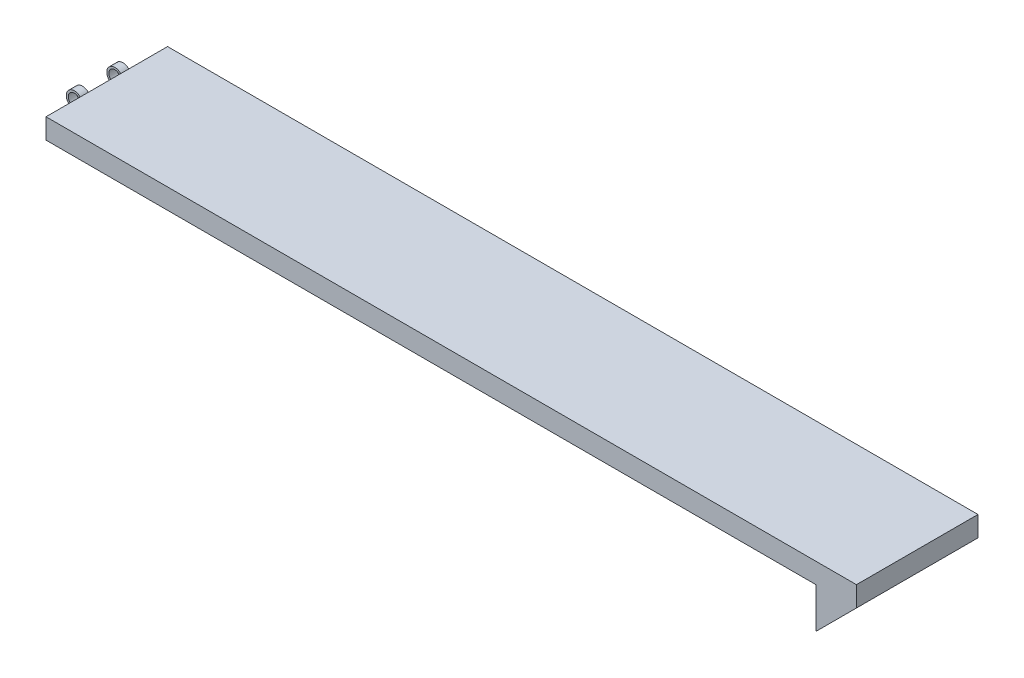
SolidWorks part; units mm, degrees
ref_plane "Front Plane" through (0, 0, 0) normal (0, 0, 1) x (1, 0, 0)
ref_plane "Top Plane" through (0, 0, 0) normal (0, 1, 0) x (1, 0, 0)
ref_plane "Right Plane" through (0, 0, 0) normal (1, 0, 0) x (0, 0, -1)
sketch "Sketch1" plane through (0, 0, 0) normal (0, 1, 0) x (1, 0, 0)
  line L1 (0, 0) -> (254, 0)
  line L2 (0, 0) -> (0, 38.1)
  line L3 (0, 38.1) -> (254, 38.1)
  line L4 (254, 0) -> (254, 38.1)
  dimension "D1" = 254
  dimension "D2" = 38.1
extrude "Boss-Extrude1" add sketch "Sketch1" along normal blind 6.35
ref_plane "Plane1" through (0, 0, -12.7) normal (0, 0, 1) x (1, 0, 0)
sketch "Sketch2" plane through (0, 0, -12.7) normal (0, 0, 1) x (1, 0, 0)
  line L0 (0, 6.35) -> (0, 0) construction
  circle A0 centre (-2.54, 3.8728) radius 2.54
  circle A1 centre (-2.54, 3.8728) radius 1.905
  dimension "D1" = 5.08
  dimension "D3" = 3.81
  dimension "D2" = 3.8728
extrude "Boss-Extrude2" add sketch "Sketch2" along normal blind 1.27 and the other way blind 1.27 separate body
ref_plane "Plane2" through (0, 0, -19.05) normal (0, 0, 1) x (1, 0, 0)
pattern_linear "LPattern1" count 2 spacing 12.7 along (0, 0, -1) of "Boss-Extrude2"
sketch "Sketch4" plane through (0, 0, -19.05) normal (0, 0, 1) x (1, 0, 0)
  circle A5 centre (256.54, 3.8728) radius 1.905
  circle A6 centre (256.54, 3.8728) radius 2.54
  dimension "D3" = 3.81
  dimension "D4" = 5.08
  dimension "D1" = 3.8728
  dimension "D2" = 256.54
sketch "Sketch5" plane through (0, 0, 0) normal (0, -1, 0) x (1, 0, 0)
  line L0 (254, -38.1) -> (0, -38.1) construction
  line L1 (254, 0) -> (241.3, 0)
  line L2 (254, 0) -> (254, -38.1)
  line L3 (254, -38.1) -> (241.3, -38.1)
  line L4 (241.3, 0) -> (241.3, -38.1)
extrude "Boss-Extrude3" add sketch "Sketch5" along normal blind 12.7
chamfer "Chamfer1" distance 12.7 angle 45 1 edges at (254, -12.7, -19.05)
